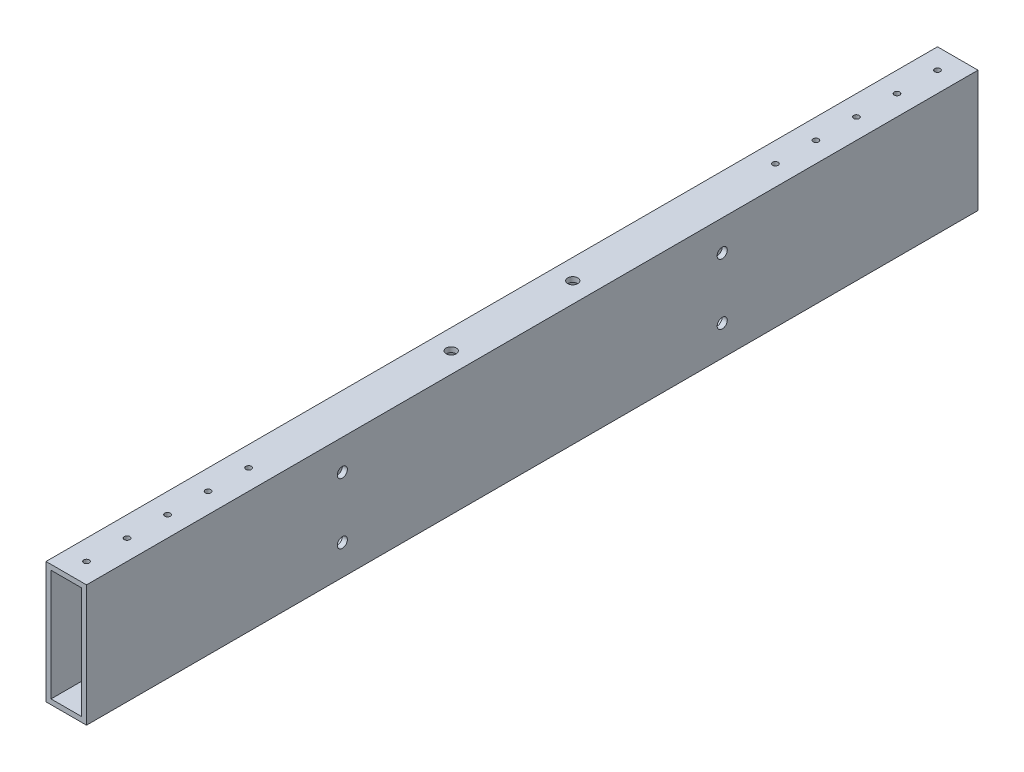
SolidWorks part; units mm, degrees
material "6061-T6 (SS)"
ref_plane "Front Plane" through (0, 0, 0) normal (0, 0, 1) x (1, 0, 0)
ref_plane "Top Plane" through (0, 0, 0) normal (0, 1, 0) x (1, 0, 0)
ref_plane "Right Plane" through (0, 0, 0) normal (1, 0, 0) x (0, 0, -1)
sketch "Sketch1" plane through (0, 0, 0) normal (0, 0, 1) x (1, 0, 0)
  line L0 (9.525, 34.925) -> (-9.525, 34.925)
  line L1 (12.7, 38.1) -> (-12.7, 38.1)
  line L2 (12.7, 38.1) -> (12.7, -38.1)
  line L3 (12.7, -38.1) -> (-12.7, -38.1)
  line L4 (-12.7, 38.1) -> (-12.7, -38.1)
  line L5 (12.7, 38.1) -> (-12.7, -38.1) construction
  line L6 (12.7, -38.1) -> (-12.7, 38.1) construction
  line L7 (-9.525, 34.925) -> (-9.525, -34.925)
  line L8 (9.525, -34.925) -> (-9.525, -34.925)
  line L9 (9.525, 34.925) -> (9.525, -34.925)
  point P0 (0, 0)
  dimension "D1" = 76.2
  dimension "D2" = 25.4
  dimension "D3" = 3.175
extrude "Boss-Extrude1" add sketch "Sketch1" along normal mid plane 558.8
sketch "Sketch2" plane through (0, 38.1, 0) normal (0, 1, 0) x (1, 0, 0)
  line L1 (12.7, 279.4) -> (-12.7, 279.4) construction
  circle A0 centre (0, 266.7) radius 1.7272
  circle A1 centre (0, 241.3) radius 1.7272
  circle A2 centre (0, 215.9) radius 1.7272
  circle A3 centre (0, 190.5) radius 1.7272
  circle A8 centre (0, 165.1) radius 1.7272
  dimension "D1" = 3.4544
  dimension "D2" = 12.7
  dimension "D3" = 5
sketch "Sketch3" plane through (0, -38.1, 0) normal (0, -1, 0) x (1, 0, 0)
  line L2 (9.525, 279.4) -> (-9.525, 279.4) construction
  circle A0 centre (0, 254) radius 1.7272
  circle A1 centre (0, 203.2) radius 1.7272
  circle A2 centre (0, 152.4) radius 1.7272
  circle A3 centre (0, 101.6) radius 1.7272
  circle A4 centre (0, 50.8) radius 1.7272
  circle A5 centre (0, 0) radius 1.7272
  circle A6 centre (0, -50.8) radius 1.7272
  circle A7 centre (0, -101.6) radius 1.7272
  circle A8 centre (0, -152.4) radius 1.7272
  circle A9 centre (0, -203.2) radius 1.7272
  circle A10 centre (0, -254) radius 1.7272
  point P6 (0, 279.4)
  dimension "D1" = 3.4544
  dimension "D2" = 25.4
  dimension "D4" = 50.8
  dimension "D3" = 11
extrude "Cut-Extrude2" cut sketch "Sketch3" against normal blind 6.35
hole_wizard "1/4 (0.25) Diameter Hole1" positions "Sketch9" profile "Sketch8" hole size "1/4" standard "ANSI Inch"
sketch "Sketch9" plane through (-12.7, 0, 0) normal (-1, 0, 0) x (0, 0, 1)
  line L0 (-119.0625, -19.05) -> (119.0625, -19.05) construction
  line L2 (279.4, -38.1) -> (-279.4, -38.1) construction
  line L3 (279.4, 38.1) -> (-279.4, 38.1) construction
  line L4 (-127, 0) -> (127, 0) construction
  point P10 (-119.0625, -19.05)
  point P11 (119.0625, -19.05)
  point P25 (-119.0625, 19.05)
  point P27 (119.0625, 19.05)
  point P34 (0, -19.05)
  dimension "D1" = 238.125
  dimension "D2" = 19.05
  dimension "D3" = 254
  dimension "D4" = 19.05
  dimension "D5" = 19.05
sketch "Sketch8" plane through (-12.7, -19.05, -119.0625) normal (0, 1, 0) x (0, 0, 1)
  line L0 (0, 0) -> (0, 27.3077)
  line L1 (0, 27.3077) -> (3.175, 25.4)
  line L2 (3.175, 25.4) -> (3.175, 0)
  line L5 (3.175, 0) -> (0, 0)
  line L10 (0, 27.3077) -> (-3.175, 25.4) construction
  line L11 (0, -6.35) -> (0, 107.95) construction
  dimension "Hole Dia." = 6.35
  dimension "Hole Depth" = 25.4
  dimension "Drill Angle" = 118
hole_wizard "1/4 (0.25) Diameter Hole2" positions "Sketch12" profile "Sketch13" hole size "1/4" standard "ANSI Inch" end condition through all
sketch "Sketch12" plane through (0, 38.1, 0) normal (0, 1, 0) x (1, 0, 0)
  line L0 (12.7, -279.4) -> (-12.7, -279.4) construction
  line L1 (0, 38.1) -> (0, -38.1) construction
  point P20 (0, -38.1)
  point P22 (0, 38.1)
  point P27 (0, -279.4)
  point P32 (0, 0)
  dimension "D7" = 76.2
sketch "Sketch13" plane through (0, 38.1, 38.1) normal (1, 0, 0) x (0, 0, 1)
  line L0 (0, 0) -> (0, 76.2)
  line L1 (0, 76.2) -> (3.175, 76.2)
  line L2 (3.175, 76.2) -> (3.175, 0)
  line L5 (3.175, 0) -> (0, 0)
  line L11 (0, -6.35) -> (0, 107.95) construction
  dimension "Thru Hole Dia." = 6.35
  dimension "Thru Hole Depth" = 76.2
extrude "Cut-Extrude4" cut sketch "Sketch2" against normal blind 6.35
mirror "Mirror1" about plane through (0, 0, 0) normal (0, 0, 1) of "Cut-Extrude4"
